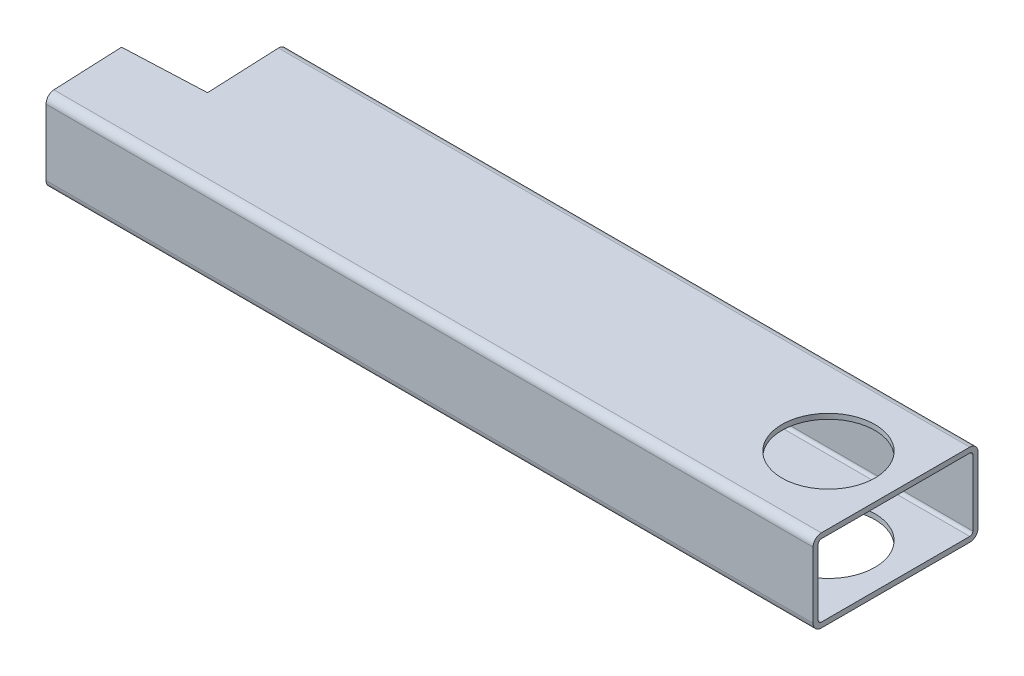
SolidWorks part; units mm, degrees
material "6061 Alloy"
ref_plane "Front" through (0, 0, 0) normal (0, 0, 1) x (1, 0, 0)
ref_plane "Top" through (0, 0, 0) normal (0, 1, 0) x (1, 0, 0)
ref_plane "Right" through (0, 0, 0) normal (1, 0, 0) x (0, 0, -1)
sketch "Sketch1" plane through (0, 0, 0) normal (1, 0, 0) x (0, 0, -1)
  line L1 (-2.54, 0) -> (-48.26, 0)
  line L2 (0, 2.54) -> (0, 22.86)
  line L3 (-2.54, 25.4) -> (-48.26, 25.4)
  line L4 (-50.8, 2.54) -> (-50.8, 22.86)
  arc A0 (-50.8, 2.54) -> (-48.26, 0) centre (-48.26, 2.54) ccw
  arc A1 (-2.54, 0) -> (0, 2.54) centre (-2.54, 2.54) ccw
  arc A2 (0, 22.86) -> (-2.54, 25.4) centre (-2.54, 22.86) ccw
  arc A3 (-48.26, 25.4) -> (-50.8, 22.86) centre (-48.26, 22.86) ccw
  point P7 (-50.8, 0)
  point P10 (0, 0)
  point P13 (0, 25.4)
  dimension "D3" = 2.54
  dimension "D1" = 25.4
  dimension "D2" = 50.8
extrude "Extrude-Thin1" add sketch "Sketch1" against normal blind 243.6368 thin thin type one direction reverse wall 1.5875
sketch "Sketch3" plane through (0, 25.4, 0) normal (0, 1, 0) x (1, 0, 0)
  line L0 (0, 49.2125) -> (79.6022, 243.0747)
  line L1 (0, -1.5875) -> (25.4, -1.5875)
  line L2 (0, -1.5875) -> (0, 49.2125)
  line L3 (0, 49.2125) -> (25.4, 49.2125)
  line L4 (25.4, -1.5875) -> (25.4, 49.2125)
  line L5 (79.6022, 243.0747) -> (126.5949, 223.7789)
  line L6 (126.5949, 223.7789) -> (34.0567, -1.5875)
  line L7 (71.7537, 223.9604) -> (118.7463, 204.6646) construction
  line L8 (95.25, 214.3125) -> (0, 214.3125)
  line L9 (0, 49.2125) -> (0, 289.0515)
  line L10 (25.4, -1.5875) -> (34.0567, -1.5875)
  circle A0 centre (95.25, 214.3125) radius 14.3129
  point P11 (95.25, 214.3125)
  dimension "D4" = 28.6258
  dimension "D5" = 6.35
  dimension "D1" = 25.4
  dimension "D2" = 50.8
  dimension "D3" = 50.8
  dimension "D6" = 95.25
  dimension "D7" = 165.1
  dimension "D8" = 243.6254
  dimension "D9" = 209.5687
sketch "Sketch4" plane through (0, 25.4, 0) normal (0, 1, 0) x (1, 0, 0)
  line L0 (-20.6629, -48.26) -> (-20.6629, -2.54) construction
  line L2 (-243.6368, -2.54) -> (0, -2.54) construction
  line L3 (-243.6368, -48.26) -> (0, -48.26) construction
  line L4 (0, -2.54) -> (0, -48.26) construction
  line L5 (0, 0) -> (-213.0114, 0) construction
  line L6 (-243.6368, 0) -> (0, 0) construction
  line L7 (-213.0114, 0) -> (-211.9163, -25.3764)
  line L8 (-211.9163, -25.3764) -> (-237.2868, -26.4712)
  line L9 (-237.2868, -26.4712) -> (-236.2369, -50.8)
  line L10 (-243.6368, -50.8) -> (0, -50.8) construction
  line L11 (-213.0114, 0) -> (-243.6368, 0)
  line L12 (-243.6368, 0) -> (-243.6368, -26.7453)
  line L13 (-236.2369, -50.8) -> (-243.6368, -50.8)
  line L14 (-243.6368, -50.8) -> (-243.6368, -26.7453)
  line L15 (-243.6368, -26.7453) -> (-211.9163, -25.3764) construction
  line L16 (-213.0114, 0) -> (-213.5234, 11.8635) construction
  line L17 (-213.5234, 11.8635) -> (40.366, 22.8201) construction
  circle A0 centre (-20.6629, -25.4) radius 14.3129
  point P5 (-20.6629, -25.4)
  dimension "D1" = 28.6258
  dimension "D2" = 6.35
  dimension "D8" = 45.544
  dimension "D3" = 25.4
  dimension "D4" = 31.75
  dimension "D6" = 6.35
  dimension "D7" = 11.8745
extrude "Cut-Extrude1" cut sketch "Sketch4" against normal through all and the other way through all
sketch "Sketch9" [suppressed] plane through (0, 25.4, 0) normal (0, 1, 0) x (1, 0, 0)
  line L0 (-214.249, -25.477) -> (-212.017, -23.0437) construction
  line L1 (-211.9163, -25.3764) -> (-212.9018, -2.54) construction
  line L3 (-237.2868, -26.4712) -> (-211.9163, -25.3764) construction
  line L4 (-211.9163, -25.3764) -> (-212.9583, -24.4206) construction
  circle A0 centre (-212.9583, -24.4206) radius 1.6679
  dimension "D2" = 0.254
  dimension "D1" = 3.302
extrude "Cut-Extrude2" [suppressed] cut sketch "Sketch9" against normal through all
sketch "Sketch10" [suppressed] plane through (0, 25.4, 0) normal (0, 1, 0) x (1, 0, 0)
  line L0 (-46.0629, -25.4) -> (-20.6629, -25.4) construction
  circle A0 centre (-46.0629, -25.4) radius 4.191
  circle A2 centre (-20.6629, -25.4) radius 14.3129 construction
  dimension "D1" = 25.4
  dimension "D2" = 8.382
extrude "Cut-Extrude3" [suppressed] cut sketch "Sketch10" against normal through all
